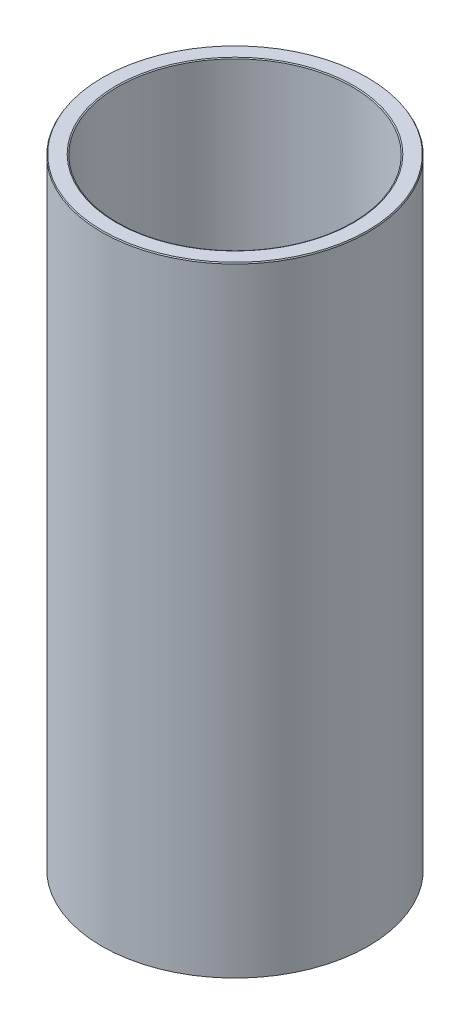
SolidWorks part; units mm, degrees
ref_plane "Front Plane" through (0, 0, 0) normal (0, 0, 1) x (1, 0, 0)
ref_plane "Top Plane" through (0, 0, 0) normal (0, 1, 0) x (1, 0, 0)
ref_plane "Right Plane" through (0, 0, 0) normal (1, 0, 0) x (0, 0, -1)
sketch "Sketch1" plane through (0, 0, 0) normal (0, 1, 0) x (1, 0, 0)
  circle A0 centre (0, 0) radius 40
  dimension "SLEEVE_OD" = 80
extrude "Boss-Extrude1" add sketch "Sketch1" along normal blind 186.2537
sketch "Sketch2" plane through (0, 0, 0) normal (0, 1, 0) x (1, 0, 0)
  circle A0 centre (0, 0) radius 35.3148
  dimension "BORE_D" = 70.6296
extrude "Cut-Extrude1" cut sketch "Sketch2" along normal through all
chamfer "Chamfer1" distance 0.336 angle 30 4 edges at (0, 186.2537, 35.3148) (0, 0, 35.3148) (0, 0, 40) (0, 186.2537, 40) first distance on face at (0, 186.2537, 35.3148) first distance on face at (0, 0, 35.3148) first distance on face at (0, 186.2537, 40)
